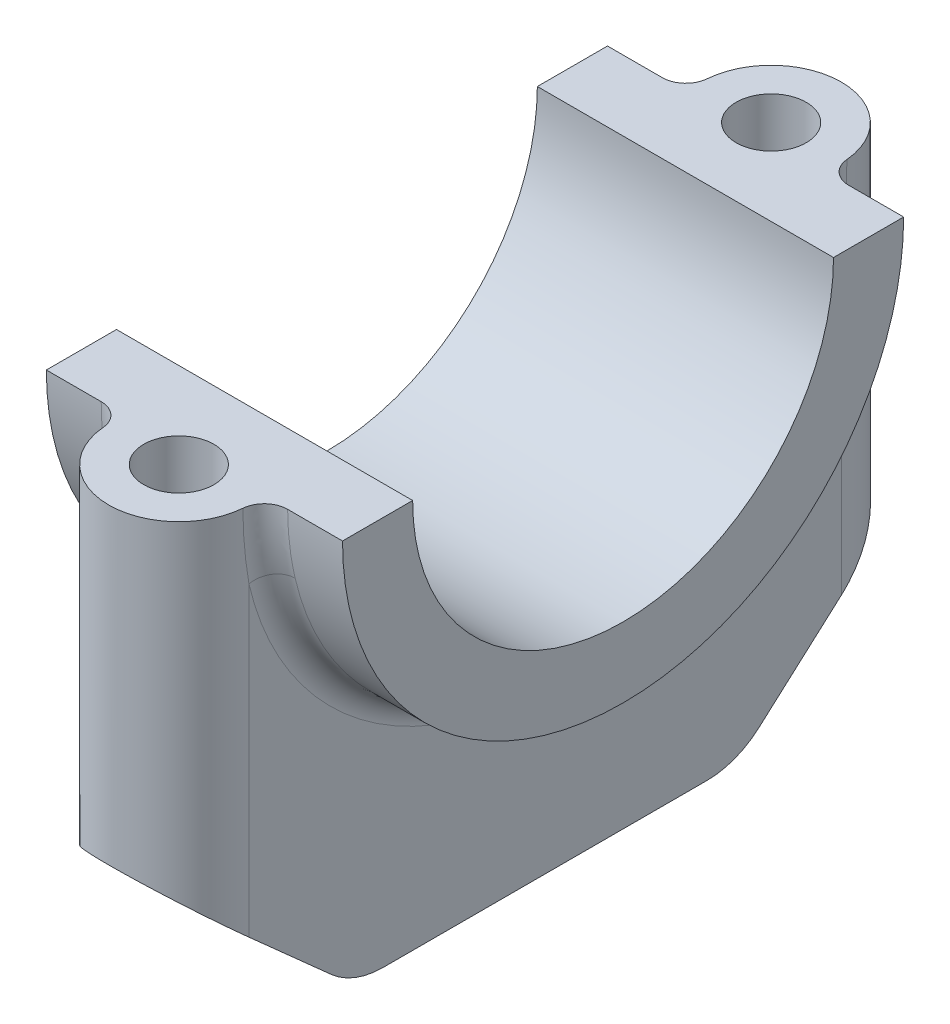
SolidWorks part; units mm, degrees
ref_plane "Front Plane" through (0, 0, 0) normal (0, 0, 1) x (1, 0, 0)
ref_plane "Top Plane" through (0, 0, 0) normal (0, 1, 0) x (1, 0, 0)
ref_plane "Right Plane" through (0, 0, 0) normal (1, 0, 0) x (0, 0, -1)
sketch "Sketch1" plane through (0, 0, 0) normal (1, 0, 0) x (0, 0, -1)
  line L0 (27, 30) -> (38, 30)
  line L1 (-38, 30) -> (-27, 30)
  line L2 (-38, 30) -> (-38, -30)
  line L3 (-38, -30) -> (38, -30)
  line L4 (38, 30) -> (38, -30)
  line L5 (-38, 30) -> (38, -30) construction
  line L6 (-38, -30) -> (38, 30) construction
  arc A0 (-36, 30) -> (36, 30) centre (0, 30) ccw
  arc A1 (-27, 30) -> (27, 30) centre (0, 30) ccw
  point P0 (0, 0)
  dimension "D1" = 76
  dimension "D2" = 60
extrude "Boss-Extrude1" add sketch "Sketch1" along normal blind 38 contours A0 L1 L2 L3 L4 L0 | A1 L0 L4 L3 L2 L1 region at (0, -11.8723, 0)
sketch "Sketch2" plane through (0, 30, 0) normal (0, 1, 0) x (1, 0, 0)
  line L0 (38, -38) -> (0, -38) construction
  line L1 (38, 38) -> (0, 38) construction
  circle A0 centre (19, -38) radius 4.5
  circle A1 centre (19, -38) radius 9
  circle A2 centre (19, 38) radius 4.5
  circle A3 centre (19, 38) radius 9
extrude "Boss-Extrude3" add sketch "Sketch2" against normal through all
sketch "Sketch4" plane through (0, 30, 0) normal (0, 1, 0) x (1, 0, 0)
  line L0 (23.5, 38) -> (14.5, 38) construction
  line L1 (23.5, -38) -> (14.5, -38) construction
  circle A1 centre (19, -38) radius 4.5
  circle A2 centre (19, 38) radius 4.5
extrude "Cut-Extrude1" cut sketch "Sketch4" against normal through all
sketch "Sketch5" plane through (0, 0, 0) normal (-1, 0, 0) x (0, 0, 1)
  line L0 (-47, -30) -> (-24.5795, -30)
  line L1 (-47, -30) -> (-38, -30) construction
  line L2 (-47, 30) -> (-47, -30) construction
  line L3 (38, -30) -> (-38, -30) construction
  line L4 (-47, -30) -> (-47, -10)
  line L5 (-47, -10) -> (-24.5795, -30)
  line L6 (0, 0) -> (0, -31.7487)
  line L7 (47, -30) -> (24.5795, -30)
  line L8 (47, -30) -> (47, -10)
  line L9 (47, -10) -> (24.5795, -30)
extrude "Cut-Extrude4" cut sketch "Sketch5" against normal through all contours L8 L9 L7 | L9 | L5 L9 | L5 L4 L0 L9 region at (0, -23.3333, -39.5265) region at (0, -23.3333, 39.5265)
fillet "Fillet1" radius 10 2 edges at (19, -30, 24.5795) (19, -30, -24.5795)
extrude "Cut-Extrude5" cut sketch "Sketch1<3>" along normal blind 10 contours A0 L1 L2 L3 L4 L0 region at (0, -11.8723, 0)
sketch "Sketch1<3>" plane through (0, 0, 0) normal (1, 0, 0) x (0, 0, -1) same geometry as "Sketch1"
sketch "Sketch7" plane through (38, 0, 0) normal (1, 0, 0) x (0, 0, -1)
  circle A0 centre (0, 30) radius 36
extrude "Cut-Extrude6" cut sketch "Sketch7" against normal blind 10 flip side to cut
ref_plane "Plane2" through (10, 30, 36) normal (0, 0, -1) x (-1, 0, 0)
fillet "Fillet2" radius 3 2 edges at (10, -6, 0) (28, -6, 0)
